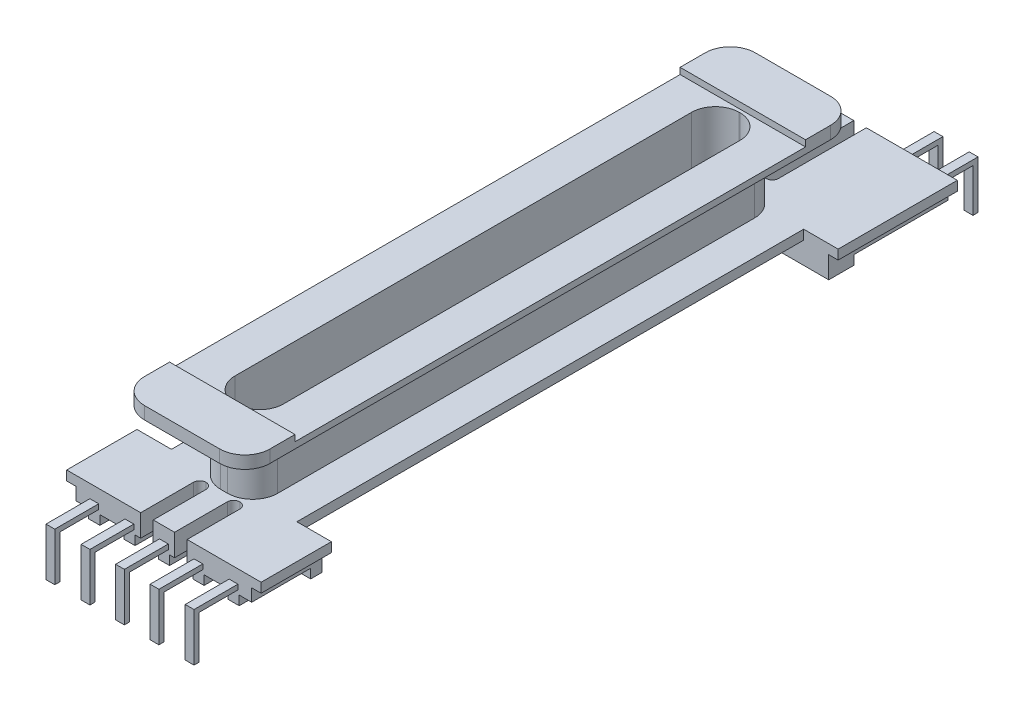
SolidWorks part; units mm, degrees
ref_plane "前视基准面" through (0, 0, 0) normal (0, 0, 1) x (1, 0, 0)
ref_plane "上视基准面" through (0, 0, 0) normal (0, 1, 0) x (1, 0, 0)
ref_plane "右视基准面" through (0, 0, 0) normal (1, 0, 0) x (0, 0, -1)
sketch "草图1" plane through (0, 0, 0) normal (0, 1, 0) x (1, 0, 0)
  line L0 (15.5, 46) -> (15.5, 55.5)
  line L1 (0, 0) -> (15.5, 0)
  line L2 (0, 0) -> (0, 5.6)
  line L3 (0, 55.5) -> (15.5, 55.5)
  line L4 (15.5, 0) -> (15.5, 5.6)
  line L5 (12.75, 46) -> (15.5, 46)
  line L7 (12.75, 5.6) -> (15.5, 5.6)
  line L9 (0, 46) -> (2.75, 46)
  line L11 (0, 5.6) -> (2.75, 5.6)
  line L12 (2.75, 46) -> (2.75, 5.6)
  line L13 (0, 46) -> (0, 55.5)
  line L14 (12.75, 46) -> (12.75, 5.6)
  line L15 (7.75, -8.9232) -> (7.75, 60.8569) construction
  dimension "D1" = 15.5
  dimension "D2" = 55.5
  dimension "D3" = 9.5
  dimension "D4" = 5.6
  dimension "D5" = 10
extrude "凸台-拉伸1" add sketch "草图1" along normal blind 0.76
sketch "草图2" plane through (0, 0, 0) normal (0, -1, 0) x (1, 0, 0)
  line L0 (7.75, -67.0502) -> (7.75, 26.869) construction
  line L1 (2.75, -46) -> (2.75, -5.6) construction
  line L2 (12.75, -5.6) -> (12.75, -46) construction
  line L3 (15.5, -55.5) -> (0, -55.5) construction
  line L4 (0.75, -55.5) -> (14.75, -55.5)
  line L5 (0.75, -55.5) -> (0.75, -46)
  line L6 (0.75, -46) -> (14.75, -46)
  line L7 (14.75, -55.5) -> (14.75, -46)
  line L8 (2.75, -5.6) -> (0, -5.6) construction
  line L9 (0.75, -5.6) -> (14.75, -5.6)
  line L10 (0.75, -5.6) -> (0.75, 0)
  line L11 (0.75, 0) -> (14.75, 0)
  line L12 (14.75, -5.6) -> (14.75, 0)
  line L13 (0, 0) -> (15.5, 0) construction
  dimension "D1" = 14
extrude "凸台-拉伸2" add sketch "草图2" along normal blind 1
sketch "草图3" plane through (0, -1, 0) normal (0, -1, 0) x (1, 0, 0)
  line L0 (14.75, -55.5) -> (14.75, -46) construction
  line L1 (0.75, -46) -> (14.75, -46)
  line L2 (0.75, -46) -> (0.75, -48)
  line L3 (0.75, -48) -> (14.75, -48)
  line L4 (14.75, -46) -> (14.75, -48)
  line L5 (0.75, -55.5) -> (14.75, -55.5) construction
  line L6 (1.75, -55.5) -> (2.65, -55.5)
  line L7 (1.75, -55.5) -> (1.75, -49.6)
  line L8 (1.75, -49.6) -> (2.65, -49.6)
  line L9 (2.65, -55.5) -> (2.65, -49.6)
  line L10 (0.75, 0) -> (0.75, -5.6) construction
  line L11 (5.5, -55.5) -> (6.4, -55.5)
  line L12 (5.5, -55.5) -> (5.5, -52.7)
  line L13 (5.5, -52.7) -> (6.4, -52.7)
  line L14 (6.4, -55.5) -> (6.4, -52.7)
  line L15 (5.5, -51) -> (6.4, -51)
  line L16 (5.5, -51) -> (5.5, -49.6)
  line L17 (5.5, -49.6) -> (6.4, -49.6)
  line L18 (6.4, -51) -> (6.4, -49.6)
  line L19 (9.1, -55.5) -> (10, -55.5)
  line L20 (9.1, -55.5) -> (9.1, -52.7)
  line L21 (9.1, -52.7) -> (10, -52.7)
  line L22 (10, -55.5) -> (10, -52.7)
  line L23 (9.1, -51) -> (10, -51)
  line L24 (9.1, -51) -> (9.1, -49.6)
  line L25 (9.1, -49.6) -> (10, -49.6)
  line L26 (10, -51) -> (10, -49.6)
  line L27 (12.85, -55.5) -> (13.75, -55.5)
  line L28 (12.85, -55.5) -> (12.85, -49.6)
  line L29 (12.85, -49.6) -> (13.75, -49.6)
  line L30 (13.75, -55.5) -> (13.75, -49.6)
  line L31 (14.75, -5.6) -> (0.75, -5.6)
  line L32 (14.75, -5.6) -> (14.75, -4.7)
  line L33 (14.75, -4.7) -> (0.75, -4.7)
  line L34 (0.75, -5.6) -> (0.75, -4.7)
  line L35 (14.75, 0) -> (0.75, 0) construction
  line L36 (1.75, -3.2) -> (2.65, -3.2)
  line L37 (1.75, -3.2) -> (1.75, 0)
  line L38 (1.75, 0) -> (2.65, 0)
  line L39 (2.65, -3.2) -> (2.65, 0)
  line L40 (7.75, -56.8686) -> (7.75, 1.0837) construction
  line L41 (4.55, -2) -> (5.45, -2)
  line L42 (4.55, -2) -> (4.55, 0)
  line L43 (4.55, 0) -> (5.45, 0)
  line L44 (5.45, -2) -> (5.45, 0)
  line L45 (4.55, -3.2) -> (5.45, -3.2)
  line L46 (4.55, -3.2) -> (4.55, -2.5)
  line L47 (4.55, -2.5) -> (5.45, -2.5)
  line L48 (5.45, -3.2) -> (5.45, -2.5)
  line L49 (10.05, -2) -> (10.95, -2)
  line L50 (10.05, -2) -> (10.05, 0)
  line L51 (10.05, 0) -> (10.95, 0)
  line L52 (10.95, -2) -> (10.95, 0)
  line L53 (10.05, -3.2) -> (10.95, -3.2)
  line L54 (10.05, -3.2) -> (10.05, -2.5)
  line L55 (10.05, -2.5) -> (10.95, -2.5)
  line L56 (10.95, -3.2) -> (10.95, -2.5)
  line L57 (12.85, -3.2) -> (13.75, -3.2)
  line L58 (12.85, -3.2) -> (12.85, 0)
  line L59 (12.85, 0) -> (13.75, 0)
  line L60 (13.75, -3.2) -> (13.75, 0)
  line L61 (2.75, -46) -> (2.75, -5.6) construction
  line L62 (12.75, -5.6) -> (12.75, -46) construction
  line L64 (8.2, 0) -> (7.3, 0)
  line L65 (8.2, 0) -> (8.2, -2)
  line L66 (8.2, -2) -> (7.3, -2)
  line L67 (7.3, 0) -> (7.3, -2)
  line L68 (8.2, -2.5) -> (7.3, -2.5)
  line L69 (8.2, -2.5) -> (8.2, -3.2)
  line L70 (8.2, -3.2) -> (7.3, -3.2)
  line L71 (7.3, -2.5) -> (7.3, -3.2)
  dimension "D1" = 2
  dimension "D2" = 0.9
  dimension "D3" = 0.9
  dimension "D4" = 0.9
  dimension "D5" = 0.9
  dimension "D6" = 0.9
  dimension "D7" = 0.9
  dimension "D8" = 0.9
  dimension "D9" = 0.9
  dimension "D10" = 0.9
  dimension "D11" = 12
  dimension "D12" = 5.9
  dimension "D13" = 4.5
  dimension "D14" = 2.8
  dimension "D15" = 1.4
  dimension "D16" = 12
  dimension "D17" = 6.4
  dimension "D18" = 3.2
  dimension "D19" = 2
  dimension "D20" = 0.7
  dimension "D21" = 0.9
extrude "凸台-拉伸3" add sketch "草图3" along normal blind 0.74
sketch "草图4" plane through (0, -1, 0) normal (0, -1, 0) x (1, 0, 0)
  line L0 (0.75, -48) -> (14.75, -48) construction
  line L1 (7.25, -57.0316) -> (8.25, -57.0316)
  line L2 (7.25, -57.0316) -> (7.25, -48)
  line L3 (7.25, -48) -> (8.25, -48)
  line L4 (8.25, -57.0316) -> (8.25, -48)
  line L10 (7.75, -59.8461) -> (7.75, 22.4835) construction
  line L11 (2.75, -46) -> (2.75, -5.6) construction
  line L12 (12.75, -5.6) -> (12.75, -46) construction
  line L13 (14.75, -4.7) -> (0.75, -4.7) construction
  line L14 (9.6, 1.0177) -> (8.6, 1.0177)
  line L15 (9.6, 1.0177) -> (9.6, -4.7)
  line L16 (9.6, -4.7) -> (8.6, -4.7)
  line L17 (8.6, 1.0177) -> (8.6, -4.7)
  line L19 (6.9, 1.0177) -> (5.9, 1.0177)
  line L20 (6.9, 1.0177) -> (6.9, -4.7)
  line L21 (6.9, -4.7) -> (5.9, -4.7)
  line L22 (5.9, 1.0177) -> (5.9, -4.7)
  dimension "D1" = 1
  dimension "D2" = 1.7
  dimension "D3" = 1
  dimension "D4" = 1
extrude "切除-拉伸1" cut sketch "草图4" against normal up to surface (1.76 mm away) up to face at (7.75, 0.76, -26.45)
fillet "圆角1" radius 0.5 2 edges at (8.25, -0.12, -48) (7.25, -0.12, -48)
sketch "草图5" plane through (0, 0.76, 0) normal (0, 1, 0) x (1, 0, 0)
  line L0 (7.75, 59.1335) -> (7.75, -6.3477) construction
  line L1 (8.025, 46.8) -> (7.475, 46.8)
  line L2 (10.025, 44.8) -> (10.025, 6.8)
  line L3 (8.025, 4.8) -> (7.475, 4.8)
  line L4 (5.475, 44.8) -> (5.475, 6.8)
  line L5 (12.75, 5.6) -> (12.75, 46) construction
  line L6 (2.75, 46) -> (2.75, 5.6) construction
  line L7 (16.2599, 25.8) -> (-2.972, 25.8) construction
  line L8 (12.75, 46) -> (2.75, 46) construction
  line L9 (2.75, 5.6) -> (12.75, 5.6) construction
  arc A0 (7.475, 46.8) -> (5.475, 44.8) centre (7.475, 44.8) ccw
  arc A1 (8.025, 46.8) -> (10.025, 44.8) centre (8.025, 44.8) cw
  arc A2 (8.025, 4.8) -> (10.025, 6.8) centre (8.025, 6.8) ccw
  arc A3 (5.475, 6.8) -> (7.475, 4.8) centre (7.475, 6.8) ccw
  point P20 (10.025, 46.8)
  point P23 (10.025, 4.8)
  dimension "D3" = 2
  dimension "D1" = 42
  dimension "D2" = 4.55
extrude "凸台-拉伸4" add sketch "草图5" along normal blind 5.1
sketch "草图6" plane through (0, 5.86, 0) normal (0, 1, 0) x (1, 0, 0)
  line L0 (7.75, -9.2532) -> (7.75, 78.8149) construction
  line L1 (4.75, 1.45) -> (10.75, 1.45)
  line L2 (2.75, 3.45) -> (2.75, 48.15)
  line L3 (4.75, 50.15) -> (10.75, 50.15)
  line L4 (12.75, 3.45) -> (12.75, 48.15)
  line L5 (-8.7664, 25.8) -> (22.3021, 25.8) construction
  line L6 (7.475, 4.8) -> (8.025, 4.8) construction
  line L7 (8.025, 46.8) -> (7.475, 46.8) construction
  line L8 (5.475, 44.8) -> (5.475, 6.8) construction
  line L9 (10.025, 6.8) -> (10.025, 44.8) construction
  arc A0 (2.75, 3.45) -> (4.75, 1.45) centre (4.75, 3.45) ccw
  arc A1 (10.75, 1.45) -> (12.75, 3.45) centre (10.75, 3.45) ccw
  arc A2 (10.75, 50.15) -> (12.75, 48.15) centre (10.75, 48.15) cw
  arc A3 (4.75, 50.15) -> (2.75, 48.15) centre (4.75, 48.15) ccw
  point P18 (2.75, 1.45)
  point P23 (12.75, 50.15)
  point P26 (2.75, 50.15)
  dimension "D3" = 2
  dimension "D1" = 48.7
  dimension "D2" = 10
extrude "凸台-拉伸5" add sketch "草图6" along normal blind 0.5
sketch "草图7" plane through (0, 6.36, 0) normal (0, 1, 0) x (1, 0, 0)
  line L0 (2.75, 5.45) -> (12.75, 5.45)
  line L1 (2.75, 46.15) -> (12.75, 46.15)
  line L2 (2.75, 5.45) -> (2.75, 3.45)
  line L3 (12.75, 46.15) -> (12.75, 48.15)
  line L4 (4.75, 1.45) -> (10.75, 1.45)
  line L5 (12.75, 3.45) -> (12.75, 48.15)
  line L6 (10.75, 50.15) -> (4.75, 50.15)
  line L7 (2.75, 48.15) -> (2.75, 3.45)
  line L8 (4.75, 1.45) -> (10.75, 1.45)
  line L9 (12.75, 3.45) -> (12.75, 5.45)
  line L10 (10.75, 50.15) -> (4.75, 50.15)
  line L11 (2.75, 48.15) -> (2.75, 46.15)
  arc A4 (2.75, 3.45) -> (4.75, 1.45) centre (4.75, 3.45) ccw
  arc A5 (10.75, 1.45) -> (12.75, 3.45) centre (10.75, 3.45) ccw
  arc A6 (12.75, 48.15) -> (10.75, 50.15) centre (10.75, 48.15) ccw
  arc A7 (4.75, 50.15) -> (2.75, 48.15) centre (4.75, 48.15) ccw
  arc A8 (2.75, 3.45) -> (4.75, 1.45) centre (4.75, 3.45) ccw
  arc A9 (10.75, 1.45) -> (12.75, 3.45) centre (10.75, 3.45) ccw
  arc A10 (12.75, 48.15) -> (10.75, 50.15) centre (10.75, 48.15) ccw
  arc A11 (4.75, 50.15) -> (2.75, 48.15) centre (4.75, 48.15) ccw
  dimension "D2" = 4
  dimension "D3" = 4
  dimension "D1" = 0
extrude "凸台-拉伸6" add sketch "草图7" along normal blind 0.5
sketch "草图8" plane through (0, 6.36, 0) normal (0, 1, 0) x (1, 0, 0)
  line L0 (7.75, -4.5217) -> (7.75, 58.5353) construction
  line L1 (7.715, 5.7) -> (7.785, 5.7)
  line L2 (5.815, 7.6) -> (5.815, 44)
  line L3 (7.715, 45.9) -> (7.785, 45.9)
  line L4 (9.685, 7.6) -> (9.685, 44)
  line L5 (2.75, 46.15) -> (2.75, 5.45) construction
  line L6 (12.75, 5.45) -> (12.75, 46.15) construction
  line L7 (-1.0698, 25.8) -> (19.7417, 25.8) construction
  line L9 (12.75, 5.45) -> (2.75, 5.45) construction
  line L10 (2.75, 46.15) -> (12.75, 46.15) construction
  arc A0 (5.815, 44) -> (7.715, 45.9) centre (7.715, 44) cw
  arc A1 (7.785, 45.9) -> (9.685, 44) centre (7.785, 44) cw
  arc A2 (7.785, 5.7) -> (9.685, 7.6) centre (7.785, 7.6) ccw
  arc A3 (5.815, 7.6) -> (7.715, 5.7) centre (7.715, 7.6) ccw
  point P18 (5.815, 45.9)
  point P23 (9.685, 5.7)
  point P26 (5.815, 5.7)
  dimension "D3" = 1.9
  dimension "D1" = 3.87
  dimension "D2" = 40.2
extrude "切除-拉伸2" cut sketch "草图8" against normal blind 14.5
fillet "圆角2" radius 0.5 4 edges at (9.6, -0.12, -4.7) (8.6, -0.12, -4.7) (5.9, -0.12, -4.7) (6.9, -0.12, -4.7)
sketch "草图9" plane through (0, 0, 0) normal (0, 0, 1) x (1, 0, 0)
  line L0 (18.5114, -0.5) -> (-5.0571, -0.5) construction
  line L1 (2.2, -0.9971) -> (2.2, 0.3181) construction
  line L2 (13.65, -0.7) -> (12.95, -0.7)
  line L3 (13.65, -0.7) -> (13.65, -0.3)
  line L4 (13.65, -0.3) -> (12.95, -0.3)
  line L5 (12.95, -0.7) -> (12.95, -0.3)
  line L6 (10.85, -0.7) -> (10.15, -0.7)
  line L7 (10.85, -0.7) -> (10.85, -0.3)
  line L8 (10.85, -0.3) -> (10.15, -0.3)
  line L9 (10.15, -0.7) -> (10.15, -0.3)
  line L10 (8.1, -0.7) -> (7.4, -0.7)
  line L11 (8.1, -0.7) -> (8.1, -0.3)
  line L12 (8.1, -0.3) -> (7.4, -0.3)
  line L13 (7.4, -0.7) -> (7.4, -0.3)
  line L14 (5.35, -0.7) -> (4.65, -0.7)
  line L15 (5.35, -0.7) -> (5.35, -0.3)
  line L16 (5.35, -0.3) -> (4.65, -0.3)
  line L17 (4.65, -0.7) -> (4.65, -0.3)
  line L18 (2.55, -0.7) -> (1.85, -0.7)
  line L19 (2.55, -0.7) -> (2.55, -0.3)
  line L20 (2.55, -0.3) -> (1.85, -0.3)
  line L21 (1.85, -0.7) -> (1.85, -0.3)
  line L22 (2.65, -1.74) -> (2.65, -1) construction
  line L23 (1.75, -1.74) -> (1.75, -1) construction
  line L24 (5, -1.1133) -> (5, 0.2598) construction
  line L25 (7.75, -1.1133) -> (7.75, 0.4617) construction
  line L26 (10.5, -0.8442) -> (10.5, -0.039) construction
  line L27 (13.3, -0.9141) -> (13.3, 0.2598) construction
  line L28 (13.75, -1.74) -> (13.75, -1) construction
  line L29 (12.85, -1.74) -> (12.85, -1) construction
  line L30 (10.95, -1.74) -> (10.95, -1) construction
  line L31 (10.05, -1.74) -> (10.05, -1) construction
  line L32 (8.2, -1.74) -> (8.2, -1) construction
  line L33 (7.3, -1.74) -> (7.3, -1) construction
  line L34 (5.45, -1.74) -> (5.45, -1) construction
  line L35 (4.55, -1.74) -> (4.55, -1) construction
  line L36 (1.75, -1) -> (0.75, -1) construction
  line L37 (0, 0) -> (0.75, 0) construction
  dimension "D1" = 0.4
  dimension "D2" = 0.7
  dimension "D3" = 0.7
  dimension "D4" = 0.7
  dimension "D5" = 0.7
  dimension "D6" = 0.7
extrude "凸台-拉伸7" add sketch "草图9" along normal blind 3.5
sketch "草图10" plane through (0, 0, -55.5) normal (0, 0, -1) x (-1, 0, 0)
  line L0 (-10.85, -0.7) -> (-10.85, -0.3) construction
  line L1 (-10.85, -0.3) -> (-10.15, -0.3) construction
  line L2 (-10.15, -0.3) -> (-10.15, -0.7) construction
  line L3 (-10.15, -0.7) -> (-10.85, -0.7) construction
  line L4 (-13.65, -0.7) -> (-13.65, -0.3) construction
  line L5 (-13.65, -0.3) -> (-12.95, -0.3) construction
  line L6 (-12.95, -0.3) -> (-12.95, -0.7) construction
  line L7 (-12.95, -0.7) -> (-13.65, -0.7) construction
  line L8 (-10.85, -0.7) -> (-10.85, -0.3)
  line L9 (-10.85, -0.3) -> (-10.15, -0.3)
  line L10 (-10.15, -0.3) -> (-10.15, -0.7)
  line L11 (-10.15, -0.7) -> (-10.85, -0.7)
  line L12 (-13.65, -0.7) -> (-13.65, -0.3)
  line L13 (-13.65, -0.3) -> (-12.95, -0.3)
  line L14 (-12.95, -0.3) -> (-12.95, -0.7)
  line L15 (-12.95, -0.7) -> (-13.65, -0.7)
extrude "凸台-拉伸8" add sketch "草图10" along normal blind 3.5
sketch "草图11" plane through (0, -0.7, 0) normal (0, -1, 0) x (1, 0, 0)
  line L0 (10.85, -59) -> (10.85, -55.5) construction
  line L1 (10.15, -59) -> (10.85, -59)
  line L2 (10.15, -59) -> (10.15, -58.6)
  line L3 (10.15, -58.6) -> (10.85, -58.6)
  line L4 (10.85, -59) -> (10.85, -58.6)
  line L5 (13.65, -59) -> (13.65, -55.5) construction
  line L6 (12.95, -59) -> (13.65, -59)
  line L7 (12.95, -59) -> (12.95, -58.6)
  line L8 (12.95, -58.6) -> (13.65, -58.6)
  line L9 (13.65, -59) -> (13.65, -58.6)
  line L10 (12.95, 3.5) -> (12.95, 0) construction
  line L11 (13.65, 3.5) -> (12.95, 3.5)
  line L12 (13.65, 3.5) -> (13.65, 3.1)
  line L13 (13.65, 3.1) -> (12.95, 3.1)
  line L14 (12.95, 3.5) -> (12.95, 3.1)
  line L15 (10.15, 3.5) -> (10.15, 0) construction
  line L16 (10.85, 3.5) -> (10.15, 3.5)
  line L17 (10.85, 3.5) -> (10.85, 3.1)
  line L18 (10.85, 3.1) -> (10.15, 3.1)
  line L19 (10.15, 3.5) -> (10.15, 3.1)
  line L20 (7.4, 3.5) -> (7.4, 0) construction
  line L21 (8.1, 3.5) -> (7.4, 3.5)
  line L22 (8.1, 3.5) -> (8.1, 3.1)
  line L23 (8.1, 3.1) -> (7.4, 3.1)
  line L24 (7.4, 3.5) -> (7.4, 3.1)
  line L25 (4.65, 3.5) -> (4.65, 0) construction
  line L26 (5.35, 3.5) -> (4.65, 3.5)
  line L27 (5.35, 3.5) -> (5.35, 3.1)
  line L28 (5.35, 3.1) -> (4.65, 3.1)
  line L29 (4.65, 3.5) -> (4.65, 3.1)
  line L30 (1.85, 3.5) -> (1.85, 0) construction
  line L31 (2.55, 3.5) -> (1.85, 3.5)
  line L32 (2.55, 3.5) -> (2.55, 3.1)
  line L33 (2.55, 3.1) -> (1.85, 3.1)
  line L34 (1.85, 3.5) -> (1.85, 3.1)
  dimension "D1" = 0.4
  dimension "D2" = 0.4
extrude "凸台-拉伸9" add sketch "草图11" along normal blind 3.44
